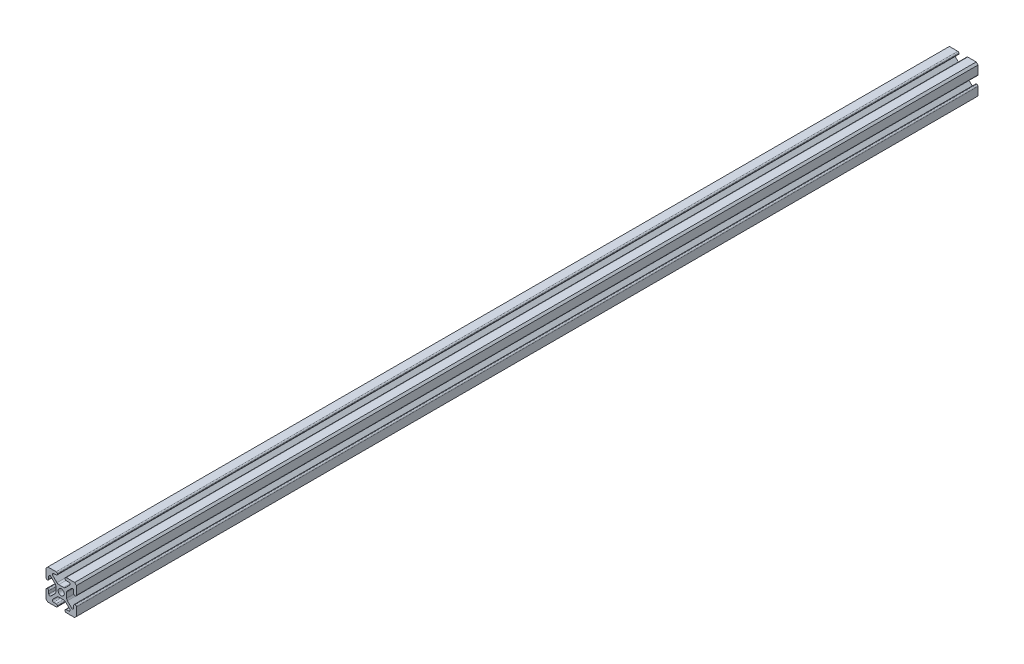
SolidWorks part; units mm, degrees
ref_plane "Front Plane" through (0, 0, 0) normal (0, 0, 1) x (1, 0, 0)
ref_plane "Top Plane" through (0, 0, 0) normal (0, 1, 0) x (1, 0, 0)
ref_plane "Right Plane" through (0, 0, 0) normal (1, 0, 0) x (0, 0, -1)
other "Configuration Table"
sketch "Sketch1" plane through (0, 0, 0) normal (0, 0, 1) x (1, 0, 0)
  line L0 (-11.2, -12.7) -> (-4.2223, -12.7)
  line L1 (-3.2063, -11.684) -> (-3.2063, -11.4407)
  line L2 (-4.2223, -10.4247) -> (-6.4093, -10.4247)
  line L3 (-7.1277, -8.6902) -> (-3.5932, -5.1557)
  line L4 (-2.0306, -4.5085) -> (2.0306, -4.5085)
  line L5 (3.5932, -5.1557) -> (7.1277, -8.6902)
  line L6 (6.4093, -10.4247) -> (4.2223, -10.4247)
  line L7 (3.2063, -11.4407) -> (3.2063, -11.684)
  line L8 (4.2223, -12.7) -> (11.2, -12.7)
  line L9 (11.2, -12.7) -> (12.7, -11.2)
  line L10 (12.7, -11.2) -> (12.7, -4.2223)
  line L11 (11.684, -3.2063) -> (11.4407, -3.2063)
  line L12 (10.4247, -4.2223) -> (10.4247, -6.4093)
  line L13 (8.6902, -7.1277) -> (5.1557, -3.5932)
  line L14 (4.5085, -2.0306) -> (4.5085, 2.0306)
  line L15 (5.1557, 3.5932) -> (8.6902, 7.1277)
  line L16 (10.4247, 6.4093) -> (10.4247, 4.2223)
  line L17 (11.4407, 3.2063) -> (11.684, 3.2063)
  line L18 (12.7, 4.2223) -> (12.7, 11.2)
  line L19 (12.7, 11.2) -> (11.2, 12.7)
  line L20 (11.2, 12.7) -> (4.2223, 12.7)
  line L21 (3.2063, 11.684) -> (3.2063, 11.4407)
  line L22 (4.2223, 10.4247) -> (6.4093, 10.4247)
  line L23 (7.1277, 8.6902) -> (3.5932, 5.1557)
  line L24 (2.0306, 4.5085) -> (-2.0306, 4.5085)
  line L25 (-3.5932, 5.1557) -> (-7.1277, 8.6902)
  line L26 (-6.4093, 10.4247) -> (-4.2223, 10.4247)
  line L27 (-3.2063, 11.4407) -> (-3.2063, 11.684)
  line L28 (-4.2223, 12.7) -> (-11.2, 12.7)
  line L29 (-11.2, 12.7) -> (-12.7, 11.2)
  line L30 (-12.7, 11.2) -> (-12.7, 4.2223)
  line L31 (-11.684, 3.2063) -> (-11.4407, 3.2063)
  line L32 (-10.4247, 4.2223) -> (-10.4247, 6.4093)
  line L33 (-8.6902, 7.1277) -> (-5.1557, 3.5932)
  line L34 (-4.5085, 2.0306) -> (-4.5085, -2.0306)
  line L35 (-5.1557, -3.5932) -> (-8.6902, -7.1277)
  line L36 (-10.4247, -6.4093) -> (-10.4247, -4.2223)
  line L37 (-11.4407, -3.2063) -> (-11.684, -3.2063)
  line L38 (-12.7, -4.2223) -> (-12.7, -11.2)
  line L39 (-12.7, -11.2) -> (-11.2, -12.7)
  arc A0 (-2.555, 0) -> (2.555, 0) centre (0, 0) ccw
  arc A1 (2.555, 0) -> (-2.555, 0) centre (0, 0) ccw
  arc A2 (-4.2223, -12.7) -> (-3.2063, -11.684) centre (-4.2223, -11.684) ccw
  arc A3 (-3.2063, -11.4407) -> (-4.2223, -10.4247) centre (-4.2223, -11.4407) ccw
  arc A4 (-7.1277, -8.6902) -> (-6.4093, -10.4247) centre (-6.4093, -9.4087) ccw
  arc A5 (-2.0306, -4.5085) -> (-3.5932, -5.1557) centre (-2.0306, -6.7183) ccw
  arc A6 (3.5932, -5.1557) -> (2.0306, -4.5085) centre (2.0306, -6.7183) ccw
  arc A7 (7.4253, -9.4087) -> (7.1277, -8.6902) centre (6.4093, -9.4087) ccw
  arc A8 (6.4093, -10.4247) -> (7.4253, -9.4087) centre (6.4093, -9.4087) ccw
  arc A9 (4.2223, -10.4247) -> (3.2063, -11.4407) centre (4.2223, -11.4407) ccw
  arc A10 (3.2063, -11.684) -> (4.2223, -12.7) centre (4.2223, -11.684) ccw
  arc A11 (12.7, -4.2223) -> (11.684, -3.2063) centre (11.684, -4.2223) ccw
  arc A12 (11.4407, -3.2063) -> (10.4247, -4.2223) centre (11.4407, -4.2223) ccw
  arc A13 (8.6902, -7.1277) -> (10.4247, -6.4093) centre (9.4087, -6.4093) ccw
  arc A14 (4.5085, -2.0306) -> (5.1557, -3.5932) centre (6.7183, -2.0306) ccw
  arc A15 (5.1557, 3.5932) -> (4.5085, 2.0306) centre (6.7183, 2.0306) ccw
  arc A16 (9.4087, 7.4253) -> (8.6902, 7.1277) centre (9.4087, 6.4093) ccw
  arc A17 (10.4247, 6.4093) -> (9.4087, 7.4253) centre (9.4087, 6.4093) ccw
  arc A18 (10.4247, 4.2223) -> (11.4407, 3.2063) centre (11.4407, 4.2223) ccw
  arc A19 (11.684, 3.2063) -> (12.7, 4.2223) centre (11.684, 4.2223) ccw
  arc A20 (4.2223, 12.7) -> (3.2063, 11.684) centre (4.2223, 11.684) ccw
  arc A21 (3.2063, 11.4407) -> (4.2223, 10.4247) centre (4.2223, 11.4407) ccw
  arc A22 (7.1277, 8.6902) -> (6.4093, 10.4247) centre (6.4093, 9.4087) ccw
  arc A23 (2.0306, 4.5085) -> (3.5932, 5.1557) centre (2.0306, 6.7183) ccw
  arc A24 (-3.5932, 5.1557) -> (-2.0306, 4.5085) centre (-2.0306, 6.7183) ccw
  arc A25 (-7.4253, 9.4087) -> (-7.1277, 8.6902) centre (-6.4093, 9.4087) ccw
  arc A26 (-6.4093, 10.4247) -> (-7.4253, 9.4087) centre (-6.4093, 9.4087) ccw
  arc A27 (-4.2223, 10.4247) -> (-3.2063, 11.4407) centre (-4.2223, 11.4407) ccw
  arc A28 (-3.2063, 11.684) -> (-4.2223, 12.7) centre (-4.2223, 11.684) ccw
  arc A29 (-12.7, 4.2223) -> (-11.684, 3.2063) centre (-11.684, 4.2223) ccw
  arc A30 (-11.4407, 3.2063) -> (-10.4247, 4.2223) centre (-11.4407, 4.2223) ccw
  arc A31 (-8.6902, 7.1277) -> (-10.4247, 6.4093) centre (-9.4087, 6.4093) ccw
  arc A32 (-4.5085, 2.0306) -> (-5.1557, 3.5932) centre (-6.7183, 2.0306) ccw
  arc A33 (-5.1557, -3.5932) -> (-4.5085, -2.0306) centre (-6.7183, -2.0306) ccw
  arc A34 (-9.4087, -7.4253) -> (-8.6902, -7.1277) centre (-9.4087, -6.4093) ccw
  arc A35 (-10.4247, -6.4093) -> (-9.4087, -7.4253) centre (-9.4087, -6.4093) ccw
  arc A36 (-10.4247, -4.2223) -> (-11.4407, -3.2063) centre (-11.4407, -4.2223) ccw
  arc A37 (-11.684, -3.2063) -> (-12.7, -4.2223) centre (-11.684, -4.2223) ccw
extrude "Boss-Extrude1" add sketch "Sketch1" along normal blind 752.4
equation "\"Extrusion Length\"= 24"
